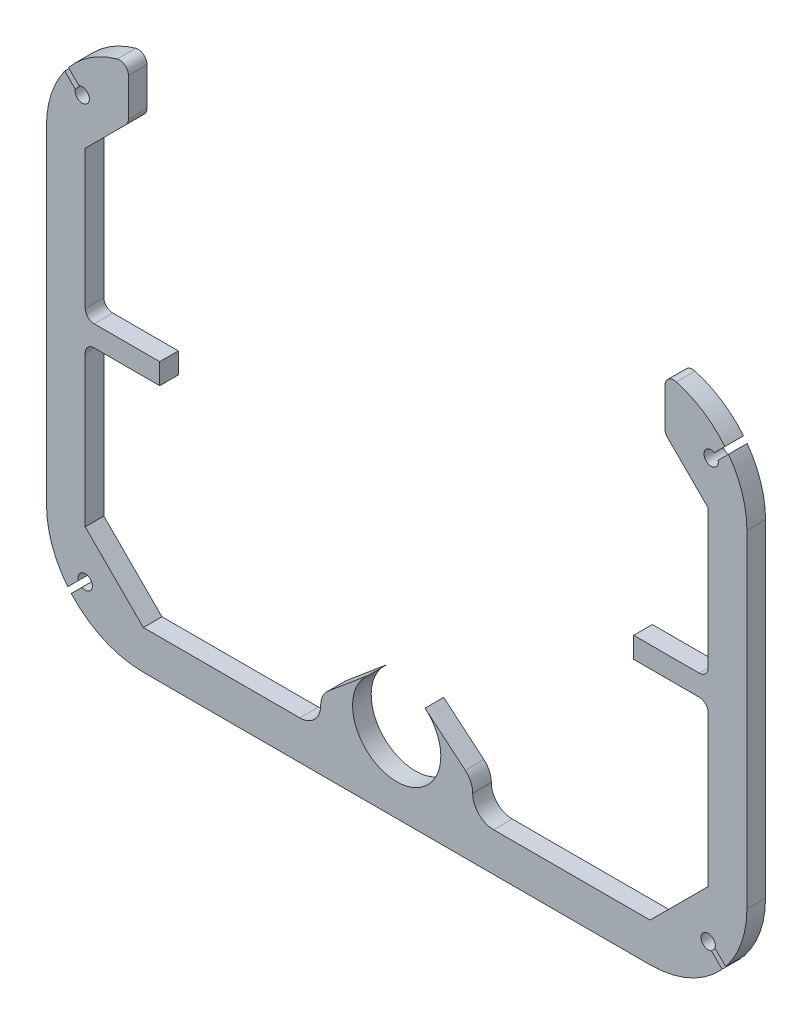
SolidWorks part; units mm, degrees
material "Delrin 2700 NC010, Low Viscosity Acetal Copolymer (SS)"
ref_plane "Front Plane" through (0, 0, 0) normal (0, 0, 1) x (1, 0, 0)
ref_plane "Top Plane" through (0, 0, 0) normal (0, 1, 0) x (1, 0, 0)
ref_plane "Right Plane" through (0, 0, 0) normal (1, 0, 0) x (0, 0, -1)
sketch "Sketch1" plane through (0, 0, 0) normal (0, 0, 1) x (1, 0, 0)
  line L0 (-21.59, -18.923) -> (-9.6321, -18.923)
  line L1 (21.59, 22.225) -> (-21.59, 22.225)
  line L2 (29.845, 13.97) -> (29.845, -13.97)
  line L3 (21.59, -22.225) -> (-21.59, -22.225)
  line L4 (-29.845, 13.97) -> (-29.845, -13.97)
  line L5 (29.845, 22.225) -> (-29.845, -22.225) construction
  line L6 (29.845, -22.225) -> (-29.845, 22.225) construction
  line L7 (9.6321, -18.923) -> (21.59, -18.923)
  line L8 (-26.543, -0.381) -> (-20.193, -0.381)
  line L9 (26.543, 1.397) -> (20.193, 1.397)
  line L10 (-26.543, 13.97) -> (-26.543, -13.97)
  line L11 (-1000, 0) -> (49000, 0) construction
  line L12 (-26.543, 0) -> (-26.543, -1.27)
  line L13 (26.543, 13.97) -> (26.543, -13.97)
  line L14 (21.59, 18.923) -> (-21.59, 18.923)
  line L15 (26.543, 1.397) -> (26.543, -0.381)
  line L16 (26.543, -0.381) -> (20.193, -0.381)
  line L17 (20.193, 1.397) -> (20.193, -0.381)
  line L18 (0, 18.923) -> (0, -18.415) construction
  line L19 (-20.193, 1.397) -> (-20.193, -0.381)
  line L20 (-26.543, 1.397) -> (-20.193, 1.397)
  line L21 (2.4164, -12.8683) -> (9.6321, -18.923)
  line L22 (-2.4164, -12.8683) -> (-9.6321, -18.923)
  line L23 (26.543, 13.97) -> (21.59, 18.923)
  line L24 (-21.59, 18.923) -> (-26.543, 13.97)
  line L25 (26.543, -13.97) -> (21.59, -18.923)
  line L27 (-26.543, -13.97) -> (-21.59, -18.923)
  line L36 (21.59, -18.923) -> (-21.59, -18.923) construction
  arc A0 (-2.4164, -12.8683) -> (2.4164, -12.8683) centre (0, -15.748) ccw
  arc A1 (-21.59, 22.225) -> (-29.845, 13.97) centre (-21.59, 13.97) ccw
  arc A2 (21.59, 22.225) -> (29.845, 13.97) centre (21.59, 13.97) cw
  arc A3 (29.845, -13.97) -> (21.59, -22.225) centre (21.59, -13.97) cw
  arc A4 (-21.59, -22.225) -> (-29.845, -13.97) centre (-21.59, -13.97) cw
  arc A13 (-21.59, -18.923) -> (-26.543, -13.97) centre (-21.59, -13.97) cw construction
  arc A14 (26.543, -13.97) -> (21.59, -18.923) centre (21.59, -13.97) cw construction
  arc A17 (21.59, 18.923) -> (26.543, 13.97) centre (21.59, 13.97) cw construction
  arc A18 (-21.59, 18.923) -> (-26.543, 13.97) centre (-21.59, 13.97) ccw construction
  point P0 (0, 0)
  dimension "D4" = 7.5184
  dimension "D6" = 8.255
  dimension "D7" = 8.255
  dimension "D8" = 8.255
  dimension "D9" = 8.255
  dimension "D1" = 59.69
  dimension "D2" = 44.45
  dimension "D10" = 3.302
  dimension "D3" = 3.175
  dimension "D13" = 15.748
  dimension "D14" = 1.778
  dimension "D15" = 21.844
  dimension "D16" = 6.35
extrude "Boss-Extrude1" add sketch "Sketch1" along normal blind 1.5875 contours A4 L3 A3 L2 A2 L1 A1 L4 L25 L7 L21 A0 L22 L0 L27 L10 L24 L14 L23 L13 | L9 L17 L16 L13 | L20 L10 L8 L19 region at (-23.368, 0.508, 0) region at (23.368, 0.508, 0) region at (26.9009, 19.2809, 0)
sketch "Sketch2" plane through (0, 0, 1.5875) normal (0, 0, 1) x (1, 0, 0)
  line L1 (-9.6321, -18.923) -> (-6.477, -18.923)
  line L2 (-9.6321, -18.923) -> (-9.6321, -16.2756)
  line L3 (-9.6321, -16.2756) -> (-6.477, -16.2756)
  line L4 (-6.477, -18.923) -> (-6.477, -16.2756)
  line L5 (0, -1000) -> (0, 49000) construction
  line L6 (9.6321, -18.923) -> (9.6321, -16.2756)
  line L7 (9.6321, -16.2756) -> (6.477, -16.2756)
  line L8 (6.477, -18.923) -> (6.477, -16.2756)
  line L9 (9.6321, -18.923) -> (6.477, -18.923)
  line L10 (-29.845, 13.97) -> (-29.845, -13.97) construction
  line L11 (-21.59, 18.923) -> (21.59, 18.923)
  line L12 (-22.86, 17.653) -> (-22.86, 22.225)
  line L13 (-22.86, 22.225) -> (22.86, 22.225)
  line L14 (22.86, 17.653) -> (22.86, 22.225)
  line L15 (26.543, 13.97) -> (21.59, 18.923) construction
  line L16 (21.59, 18.923) -> (-21.59, 18.923) construction
  line L17 (-2.4164, -12.8683) -> (-9.6321, -18.923) construction
  line L18 (21.59, 22.225) -> (-21.59, 22.225) construction
  line L19 (22.86, 17.653) -> (21.59, 18.923)
  line L20 (-21.59, 18.923) -> (-26.543, 13.97) construction
  line L21 (-21.59, 18.923) -> (-22.86, 17.653)
  point P25 (0, 22.225)
  dimension "D1" = 6.477
  dimension "D2" = 6.985
extrude "Cut-Extrude1" cut sketch "Sketch2" against normal up to next
fillet "Fillet1" radius 1.778 4 edges at (6.477, -18.923, 0.7937) (6.477, -16.2756, 0.7937) (-6.477, -18.923, 0.7937) (-6.477, -16.2756, 0.7937)
fillet "Fillet2" radius 0.762 4 edges at (22.86, 22.1267, 0.7937) (22.86, 17.653, 0.7937) (-22.86, 17.653, 0.7937) (-22.86, 22.1267, 0.7937)
fillet "Fillet3" radius 0.762 4 edges at (-26.543, -0.381, 0.7937) (26.543, -0.381, 0.7937) (26.543, 1.397, 0.7937) (-26.543, 1.397, 0.7937)
sketch "Sketch3" plane through (0, 0, 1.5875) normal (0, 0, 1) x (1, 0, 0)
  circle A0 centre (-25.019, -16.51) radius 0.6096 construction
  circle A1 centre (-25.019, 16.256) radius 0.6096 construction
  circle A2 centre (25.019, 16.256) radius 0.6096 construction
  circle A3 centre (25.019, -16.51) radius 0.6096 construction
  circle A4 centre (-25.019, -16.51) radius 0.6096 construction
  circle A5 centre (-25.019, 16.256) radius 0.6096 construction
  circle A6 centre (25.019, 16.256) radius 0.6096 construction
  circle A7 centre (25.019, -16.51) radius 0.6096 construction
  circle A8 centre (-26.797, 17.78) radius 0.6096
  circle A9 centre (-26.543, -18.034) radius 0.6096
  circle A10 centre (26.797, 17.78) radius 0.6096
  circle A11 centre (26.543, -18.034) radius 0.6096
  dimension "D1" = 1.524
  dimension "D2" = 1.778
  dimension "D3" = 1.524
  dimension "D4" = 1.524
  dimension "D5" = 1.778
  dimension "D6" = 1.524
extrude "Cut-Extrude2" cut sketch "Sketch3" against normal up to surface (1.5875 mm away) up to face at (0, -2.166, 0)
sketch "Sketch4" plane through (0, 0, 0) normal (0, 0, -1) x (-1, 0, 0)
  line L0 (-27.0788, 18.3206) -> (-27.9684, 19.2103)
  line L1 (-29.845, 13.97) -> (-29.845, -13.97) construction
  line L2 (-28.2812, 18.8046) -> (-27.3915, 17.9149)
  circle A1 centre (-26.797, 17.78) radius 0.6096 construction
  arc A2 (-23.8286, 21.9157) -> (-29.845, 13.97) centre (-21.59, 13.97) ccw construction
  arc A3 (-27.9684, 19.2103) -> (-28.2812, 18.8046) centre (-21.59, 13.97) ccw
  arc A4 (-27.0788, 18.3206) -> (-27.3915, 17.9149) centre (-26.797, 17.78) ccw
  dimension "D1" = 0.508
  dimension "D2" = 135
extrude "Cut-Extrude3" cut sketch "Sketch4" against normal up to surface (1.5875 mm away) up to face at (27.1526, -18.034, 1.5875)
mirror "Mirror1" about plane through (0, 0, 0) normal (1, 0, 0) of "Cut-Extrude3"
sketch "Sketch5" plane through (0, 0, 0) normal (0, 0, -1) x (-1, 0, 0)
  line L0 (-27.1221, -18.2245) -> (-28.0309, -19.1333)
  line L1 (-8.255, -18.923) -> (-21.59, -18.923) construction
  line L2 (-27.7341, -19.4831) -> (-26.8253, -18.5743)
  circle A0 centre (-26.543, -18.034) radius 0.6096 construction
  arc A1 (-29.845, -13.97) -> (-21.59, -22.225) centre (-21.59, -13.97) ccw construction
  arc A2 (-28.0309, -19.1333) -> (-27.7341, -19.4831) centre (-21.59, -13.97) ccw
  arc A3 (-27.1221, -18.2245) -> (-26.8253, -18.5743) centre (-26.543, -18.034) ccw
  dimension "D2" = 0.4572
  dimension "D1" = 45
extrude "Cut-Extrude4" cut sketch "Sketch5" against normal through all
mirror "Mirror3" about plane through (0, 0, 0) normal (1, 0, 0) of "Cut-Extrude4"
equation "\"SnapInRodSlotSize\"= .02"
equation "\"D1@Sketch4\"=\"SnapInRodSlotSize\""
